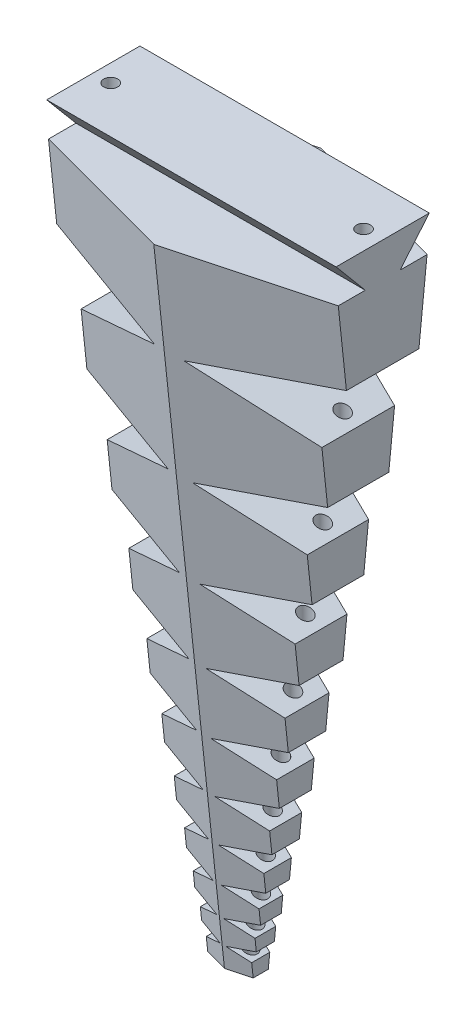
SolidWorks part; units mm, degrees
ref_plane "Front Plane" through (0, 0, 0) normal (0, 0, 1) x (1, 0, 0)
ref_plane "Top Plane" through (0, 0, 0) normal (0, 1, 0) x (1, 0, 0)
ref_plane "Right Plane" through (0, 0, 0) normal (1, 0, 0) x (0, 0, -1)
sketch "spiral_flat" plane through (0, 0, 0) normal (0, 0, 1) x (1, 0, 0)
  line L0 (3.2655, 0) -> (-3.2655, 0) construction
  line L1 (3.9293, 3.054) -> (-3.9293, 3.054) construction
  line L2 (4.728, 6.7288) -> (-4.728, 6.7288) construction
  line L3 (5.689, 11.1506) -> (-5.689, 11.1506) construction
  line L4 (6.8455, 16.4712) -> (-6.8455, 16.4712) construction
  line L5 (8.2369, 22.8733) -> (-8.2369, 22.8733) construction
  line L6 (9.9112, 30.5768) -> (-9.9112, 30.5768) construction
  line L7 (11.9259, 39.8461) -> (-11.9259, 39.8461) construction
  line L8 (14.35, 50.9996) -> (-14.35, 50.9996) construction
  line L9 (17.2669, 64.4202) -> (-17.2669, 64.4202) construction
  line L10 (20.7767, 80.5689) -> (-20.7767, 80.5689) construction
  line L11 (25, 100) -> (-25, 100) construction
  line L12 (0, -2.9617) -> (0, 103.8438) construction
  line L13 (3.2655, 0) -> (25, 100) construction
  line L14 (-3.2655, 0) -> (-25, 100) construction
  line L15 (0.3266, 0) -> (2.5, 100) construction
  line L16 (-0.3266, 0) -> (-2.5, 100) construction
  line L17 (-20.7767, 80.5689) -> (-20.7767, 100) construction
  line L18 (-17.2669, 64.4202) -> (-17.2669, 80.5689) construction
  line L19 (-14.35, 50.9996) -> (-14.35, 64.4202) construction
  line L20 (-11.9259, 39.8461) -> (-11.9259, 50.9996) construction
  line L21 (-9.9112, 30.5768) -> (-9.9112, 39.8461) construction
  line L22 (-8.2369, 22.8733) -> (-8.2369, 30.5768) construction
  line L23 (-6.8455, 16.4712) -> (-6.8455, 22.8733) construction
  line L24 (-5.689, 11.1506) -> (-5.689, 16.4712) construction
  line L25 (-4.728, 6.7288) -> (-4.728, 11.1506) construction
  line L26 (-3.9293, 3.054) -> (-3.9293, 6.7288) construction
  line L27 (-3.2655, 0) -> (-3.2655, 3.054) construction
  line L28 (20.7767, 80.5689) -> (20.7767, 100) construction
  line L29 (14.35, 50.9996) -> (14.35, 64.4202) construction
  line L30 (17.2669, 64.4202) -> (17.2669, 80.5689) construction
  line L31 (11.9259, 39.8461) -> (11.9259, 50.9996) construction
  line L32 (9.9112, 30.5768) -> (9.9112, 39.8461) construction
  line L33 (8.2369, 22.8733) -> (8.2369, 30.5768) construction
  line L34 (6.8455, 16.4712) -> (6.8455, 22.8733) construction
  line L35 (5.689, 11.1506) -> (5.689, 16.4712) construction
  line L36 (4.728, 6.7288) -> (4.728, 11.1506) construction
  line L37 (3.9293, 3.054) -> (3.9293, 6.7288) construction
  line L38 (3.2655, 0) -> (3.2655, 3.054) construction
  line L39 (-2.0777, 80.5689) -> (-17.2669, 75.0404) construction
  line L40 (-1.7267, 64.4202) -> (-17.2669, 67.1604) construction
  line L41 (-2.0777, 80.5689) -> (-20.7767, 83.866) construction
  line L42 (-1.7267, 64.4202) -> (-14.35, 59.8257) construction
  line L43 (-1.435, 50.9996) -> (-14.35, 53.2769) construction
  line L44 (-1.435, 50.9996) -> (-11.9259, 47.1812) construction
  line L45 (-1.1926, 39.8461) -> (-11.9259, 41.7387) construction
  line L46 (-1.1926, 39.8461) -> (-9.9112, 36.6728) construction
  line L47 (-0.9911, 30.5768) -> (-9.9112, 32.1496) construction
  line L48 (-0.9911, 30.5768) -> (-8.2369, 27.9395) construction
  line L49 (-0.8237, 22.8733) -> (-8.2369, 24.1805) construction
  line L50 (-0.8237, 22.8733) -> (-6.8455, 20.6816) construction
  line L51 (-0.6845, 16.4712) -> (-6.8455, 17.5576) construction
  line L52 (-0.6845, 16.4712) -> (-5.689, 14.6497) construction
  line L53 (-0.5689, 11.1506) -> (-5.689, 12.0534) construction
  line L54 (-0.5689, 11.1506) -> (-4.728, 9.6368) construction
  line L55 (-0.4728, 6.7288) -> (-4.728, 7.4791) construction
  line L56 (-0.4728, 6.7288) -> (-3.9293, 5.4708) construction
  line L57 (-0.3929, 3.054) -> (-3.9293, 3.6776) construction
  line L58 (-0.3929, 3.054) -> (-3.2655, 2.0085) construction
  line L59 (0.3929, 3.054) -> (3.2655, 2.0085) construction
  line L60 (0.3929, 3.054) -> (3.9293, 3.6776) construction
  line L61 (0.4728, 6.7288) -> (3.9293, 5.4708) construction
  line L62 (0.4728, 6.7288) -> (4.728, 7.4791) construction
  line L63 (0.5689, 11.1506) -> (4.728, 9.6368) construction
  line L64 (0.5689, 11.1506) -> (5.689, 12.0534) construction
  line L65 (0.6845, 16.4712) -> (5.689, 14.6497) construction
  line L66 (0.6845, 16.4712) -> (6.8455, 17.5576) construction
  line L67 (0.8237, 22.8733) -> (6.8455, 20.6816) construction
  line L68 (0.8237, 22.8733) -> (8.2369, 24.1805) construction
  line L69 (0.9911, 30.5768) -> (8.2369, 27.9395) construction
  line L70 (0.9911, 30.5768) -> (9.9112, 32.1496) construction
  line L71 (1.1926, 39.8461) -> (9.9112, 36.6728) construction
  line L72 (1.1926, 39.8461) -> (11.9259, 41.7387) construction
  line L73 (1.435, 50.9996) -> (11.9259, 47.1812) construction
  line L74 (1.435, 50.9996) -> (14.35, 53.2769) construction
  line L75 (1.7267, 64.4202) -> (14.35, 59.8257) construction
  line L76 (1.7267, 64.4202) -> (17.2669, 67.1604) construction
  line L77 (2.0777, 80.5689) -> (17.2669, 75.0404) construction
  line L78 (2.0777, 80.5689) -> (20.7767, 83.866) construction
  line L143 (-20.7767, 100) -> (-25, 100)
  line L144 (-25, 100) -> (-3.2655, 0)
  line L145 (-3.2655, 0) -> (-3.2655, 2.0085)
  line L146 (-0.3929, 3.054) -> (-3.9293, 3.6776)
  line L147 (-3.9293, 5.4708) -> (-0.4728, 6.7288)
  line L148 (-4.728, 7.4791) -> (-4.728, 9.6368)
  line L149 (-0.5689, 11.1506) -> (-5.689, 12.0534)
  line L150 (-5.689, 14.6497) -> (-0.6845, 16.4712)
  line L151 (-6.8455, 17.5576) -> (-6.8455, 20.6816)
  line L152 (-0.8237, 22.8733) -> (-8.2369, 24.1805)
  line L153 (-9.9112, 36.6728) -> (-1.1926, 39.8461)
  line L154 (-1.1926, 39.8461) -> (-11.9259, 41.7387)
  line L155 (-14.35, 59.8257) -> (-1.7267, 64.4202)
  line L156 (-1.7267, 64.4202) -> (-17.2669, 67.1604)
  line L157 (-17.2669, 75.0404) -> (-2.0777, 80.5689)
  line L158 (-20.7767, 83.866) -> (-20.7767, 100)
  line L159 (3.2655, 2.0085) -> (3.2655, 0)
  line L160 (0.3929, 3.054) -> (3.2655, 2.0085)
  line L161 (3.9293, 3.6776) -> (0.3929, 3.054)
  line L162 (3.9293, 5.4708) -> (3.9293, 3.6776)
  line L163 (0.4728, 6.7288) -> (3.9293, 5.4708)
  line L164 (4.728, 7.4791) -> (0.4728, 6.7288)
  line L165 (4.728, 9.6368) -> (4.728, 7.4791)
  line L166 (0.5689, 11.1506) -> (4.728, 9.6368)
  line L167 (5.689, 12.0534) -> (0.5689, 11.1506)
  line L168 (5.689, 14.6497) -> (5.689, 12.0534)
  line L169 (0.6845, 16.4712) -> (5.689, 14.6497)
  line L170 (6.8455, 17.5576) -> (0.6845, 16.4712)
  line L171 (6.8455, 20.6816) -> (6.8455, 17.5576)
  line L172 (0.8237, 22.8733) -> (6.8455, 20.6816)
  line L173 (8.2369, 24.1805) -> (0.8237, 22.8733)
  line L174 (8.2369, 27.9395) -> (8.2369, 24.1805)
  line L175 (0.9911, 30.5768) -> (8.2369, 27.9395)
  line L176 (9.9112, 32.1496) -> (0.9911, 30.5768)
  line L177 (9.9112, 36.6728) -> (9.9112, 32.1496)
  line L178 (1.1926, 39.8461) -> (9.9112, 36.6728)
  line L179 (11.9259, 41.7387) -> (1.1926, 39.8461)
  line L180 (11.9259, 47.1812) -> (11.9259, 41.7387)
  line L181 (1.435, 50.9996) -> (11.9259, 47.1812)
  line L182 (14.35, 53.2769) -> (1.435, 50.9996)
  line L183 (14.35, 59.8257) -> (14.35, 53.2769)
  line L184 (1.7267, 64.4202) -> (14.35, 59.8257)
  line L185 (17.2669, 67.1604) -> (1.7267, 64.4202)
  line L186 (17.2669, 75.0404) -> (17.2669, 67.1604)
  line L187 (2.0777, 80.5689) -> (17.2669, 75.0404)
  line L188 (20.7767, 83.866) -> (2.0777, 80.5689)
  line L189 (20.7767, 100) -> (20.7767, 83.866)
  line L190 (25, 100) -> (3.2655, 0)
  line L191 (20.7767, 100) -> (25, 100)
  line L192 (-20.7767, 83.866) -> (-2.0777, 80.5689)
  line L193 (-17.2669, 75.0404) -> (-17.2669, 67.1604)
  line L194 (-14.35, 59.8257) -> (-14.35, 53.2769)
  line L195 (-14.35, 53.2769) -> (-1.435, 50.9996)
  line L196 (-1.435, 50.9996) -> (-11.9259, 47.1812)
  line L197 (-11.9259, 47.1812) -> (-11.9259, 41.7387)
  line L198 (-9.9112, 36.6728) -> (-9.9112, 32.1496)
  line L199 (-9.9112, 32.1496) -> (-0.9911, 30.5768)
  line L200 (-0.9911, 30.5768) -> (-8.2369, 27.9395)
  line L201 (-8.2369, 27.9395) -> (-8.2369, 24.1805)
  line L202 (-6.8455, 20.6816) -> (-0.8237, 22.8733)
  line L203 (-6.8455, 17.5576) -> (-0.6845, 16.4712)
  line L204 (-5.689, 14.6497) -> (-5.689, 12.0534)
  line L205 (-0.5689, 11.1506) -> (-4.728, 9.6368)
  line L206 (-4.728, 7.4791) -> (-0.4728, 6.7288)
  line L207 (-3.9293, 5.4708) -> (-3.9293, 3.6776)
  line L208 (-0.3929, 3.054) -> (-3.2655, 2.0085)
  spline S0 degree 3 poles (0, 0) (0, 1.018) (0, 3.261) (0, 6.9778) (0, 11.4502) (0, 16.8317) (0, 23.3071) (0, 31.0987) (0, 40.4742) (0, 51.7553) (0, 65.3296) (0, 81.663) (0, 93.523) (0, 100) knots 0 0 0 0 0.03054 0.067288 0.111506 0.164712 0.228733 0.305768 0.398461 0.509996 0.644202 0.805689 1 1 1 1
  point P39 (0, 3.054)
  point P40 (0, 6.7288)
  point P41 (0, 11.1506)
  point P42 (0, 16.4712)
  point P43 (0, 22.8733)
  point P44 (0, 30.5768)
  point P45 (0, 39.8461)
  point P46 (0, 50.9996)
  point P47 (0, 64.4202)
  point P48 (0, 80.5689)
  point P49 (-0.3266, 0)
  point P50 (-0.3929, 3.054)
  point P51 (-0.4728, 6.7288)
  point P52 (-0.5689, 11.1506)
  point P53 (-0.6845, 16.4712)
  point P54 (-0.8237, 22.8733)
  point P55 (-0.9911, 30.5768)
  point P56 (-1.1926, 39.8461)
  point P57 (-1.435, 50.9996)
  point P58 (-1.7267, 64.4202)
  point P59 (-2.0777, 80.5689)
  point P60 (-2.5, 100)
  point P61 (0.3266, 0)
  point P62 (0.3929, 3.054)
  point P63 (0.4728, 6.7288)
  point P64 (0.5689, 11.1506)
  point P65 (0.6845, 16.4712)
  point P66 (0.8237, 22.8733)
  point P67 (0.9911, 30.5768)
  point P68 (1.1926, 39.8461)
  point P69 (1.435, 50.9996)
  point P70 (1.7267, 64.4202)
  point P71 (2.0777, 80.5689)
  point P72 (2.5, 100)
  dimension "D1" = 100
  dimension "D3" = 7.8586
  dimension "D2" = 6.531
  dimension "D4" = 9.456
  dimension "D5" = 11.3781
  dimension "D6" = 13.6909
  dimension "D7" = 16.4738
  dimension "D8" = 19.8224
  dimension "D9" = 23.8517
  dimension "D10" = 28.7
  dimension "D11" = 34.5338
  dimension "D12" = 41.5535
  dimension "D13" = 50
  dimension "D14" = 0.6531
  dimension "D15" = 0.7859
  dimension "D16" = 0.9456
  dimension "D17" = 1.1378
  dimension "D18" = 1.3691
  dimension "D19" = 1.6474
  dimension "D20" = 1.9822
  dimension "D21" = 2.3852
  dimension "D22" = 2.87
  dimension "D23" = 3.4534
  dimension "D24" = 4.1553
  dimension "D25" = 5
  dimension "D26" = 20
  dimension "D27" = 10
  dimension "D28" = 10
  dimension "D29" = 20
  dimension "D30" = 10
  dimension "D31" = 20
  dimension "D32" = 10
  dimension "D33" = 20
  dimension "D34" = 10
  dimension "D35" = 20
  dimension "D36" = 10
  dimension "D37" = 20
  dimension "D38" = 10
  dimension "D39" = 20
  dimension "D40" = 10
  dimension "D41" = 20
  dimension "D42" = 10
  dimension "D43" = 20
  dimension "D44" = 10
  dimension "D45" = 20
sketch "Sketch2" plane through (0, 0, 0) normal (0, 1, 0) x (1, 0, 0)
  line L0 (3.2655, 0) -> (-3.2384, 0) construction
  line L1 (0.0136, -1.9593) -> (0.0136, 1.9593) construction
  line L2 (3.2655, -1.9593) -> (3.2655, 1.9593) construction
  line L3 (-3.2384, -1.9593) -> (-3.2384, 1.9593) construction
  line L4 (3.2655, 1.9593) -> (-3.2384, 1.9593) construction
  line L5 (0.0136, 1.9593) -> (3.2655, 1.088) construction
  line L6 (3.2655, -1.9593) -> (-3.2384, -1.9593) construction
  line L7 (0.0136, -1.9593) -> (3.2655, -1.088) construction
  line L8 (0.0136, -1.9593) -> (-3.2384, -1.088) construction
  line L9 (0.0136, 1.9593) -> (-3.2384, 1.088) construction
  line L10 (0.0136, 1.9593) -> (-3.2384, 1.088)
  line L11 (-3.2384, 1.088) -> (-3.2384, -1.088)
  line L12 (-3.2384, -1.088) -> (0.0136, -1.9593)
  line L13 (0.0136, -1.9593) -> (3.2655, -1.088)
  line L14 (3.2655, -1.088) -> (3.2655, 1.088)
  line L15 (3.2655, 1.088) -> (0.0136, 1.9593)
  point P7 (0.0136, 0)
  dimension "D1" = 3.9186
  dimension "D2" = 15
ref_plane "Plane1" through (0, 100, 0) normal (0, 1, 0) x (1, 0, 0)
sketch "Sketch3" plane through (0, 100, 0) normal (0, 1, 0) x (1, 0, 0)
  line L2 (-0.1234, -12.5) -> (-0.1234, 12.5) construction
  line L5 (24.7531, 12.5) -> (-25, 12.5) construction
  line L6 (-0.1234, 12.5) -> (-25, 5.8343) construction
  line L7 (24.7531, -12.5) -> (-25, -12.5) construction
  line L8 (-0.1234, -12.5) -> (-25, -5.8343) construction
  line L9 (-0.1234, -12.5) -> (24.7531, -5.8343) construction
  line L10 (-0.1234, 12.5) -> (24.7531, 5.8343) construction
  line L12 (-25, -12.5) -> (-25, 12.5) construction
  line L15 (24.7531, -12.5) -> (24.7531, 12.5) construction
  line L16 (-0.1234, 12.5) -> (-25, 5.8343)
  line L17 (-25, 5.8343) -> (-25, -5.8343)
  line L18 (-25, -5.8343) -> (-0.1234, -12.5)
  line L19 (-0.1234, -12.5) -> (24.7531, -5.8343)
  line L20 (24.7531, -5.8343) -> (24.7531, 5.8343)
  line L21 (24.7531, 5.8343) -> (-0.1234, 12.5)
  point P8 (-0.1234, 0)
  dimension "D1" = 25
  dimension "D2" = 15
  dimension "D3" = 0.1234
  dimension "D4" = 24.8766
loft "Loft1" add profiles "Sketch2", "Sketch3" connector at (3.2655, 0, -1.0879) connector at (24.7531, 100, -5.8343)
extrude "Cut-Extrude2" cut sketch "spiral_flat" against normal through all both and the other way through all contours L192 L157 L193 L156 L155 L194 L195 L196 L197 L154 L153 L198 L199 L200 L201 L152 L202 L151 L203 L150 L204 L149 L205 L148 L206 L147 L207 L146 L208 L145 L144 L143 L158 | L188 L187 L186 L185 L184 L183 L182 L181 L180 L179 L178 L177 L176 L175 L174 L173 L172 L171 L170 L169 L168 L167 L166 L165 L164 L163 L162 L161 L160 L159 L190 L191 L189
ref_plane "Plane3" through (-20.7767, 0, 0) normal (-1, 0, 0) x (0, 0, 1)
sketch "Sketch6" plane through (-20.7767, 0, 0) normal (-1, 0, 0) x (0, 0, 1)
  line L0 (0, 100) -> (0, 83.866) construction
  line L1 (26.7585, 100) -> (-26.7585, 100) construction
  line L2 (-5.2594, 83.866) -> (5.2594, 83.866) construction
  line L3 (24.3259, 95) -> (-24.3259, 95) construction
  line L4 (2.5, 95) -> (6.6955, 100) construction
  line L5 (-2.5, 95) -> (-6.6955, 100) construction
  line L6 (2.5, 95) -> (6.6955, 100)
  line L7 (6.6955, 100) -> (6.966, 100)
  line L8 (6.966, 100) -> (5.2594, 83.866) construction
  line L9 (6.966, 100) -> (6.4371, 95)
  line L10 (6.4371, 95) -> (2.5, 95)
  line L11 (-2.5, 95) -> (-6.6955, 100)
  line L12 (-6.6955, 100) -> (-6.966, 100)
  line L13 (-6.966, 100) -> (-6.4371, 95)
  line L14 (-5.2594, 83.866) -> (-6.966, 100) construction
  line L15 (-6.4371, 95) -> (-2.5, 95)
  point P6 (0, 95)
  point P7 (-2.5, 95)
  point P10 (0, 95)
  point P11 (2.5, 95)
  dimension "D1" = 5
  dimension "D2" = 5
  dimension "D3" = 50
sketch "Sketch16" plane through (0, 0, 0) normal (0, -1, 0) x (-1, 0, 0)
  line L0 (-0.0136, -1.9593) -> (-0.0136, 1.9593) construction
  line L1 (-3.2655, 0) -> (3.2384, 0) construction
  circle A0 centre (1.7364, 0) radius 1
  circle A1 centre (-1.7636, 0) radius 1
  point P4 (-1.7636, 0)
  point P5 (1.7364, 0)
  dimension "D2" = 2
  dimension "D1" = 3.5
sketch "Sketch17" plane through (0, 100, 0) normal (0, 1, 0) x (1, 0, 0)
  line L0 (-0.1234, 12.5) -> (-0.1234, -12.5) construction
  line L1 (-20.7767, 0) -> (20.7767, 0) construction
  line L2 (-20.7767, -24.3259) -> (-20.7767, 24.3259) construction
  line L3 (20.7767, 6.8998) -> (20.7767, -6.8998) construction
  circle A1 centre (-18.2767, 0) radius 1
  circle A2 centre (18.0299, 0) radius 1
  point P10 (-18.2767, 0)
  point P17 (18.0299, 0)
  dimension "D2" = 2
  dimension "D1" = 2.5
sketch3d "3DSketch1"
  line L0 (18.0299, 100, 0) -> (1.7636, 0, 0) construction
  line L1 (-18.2767, 100, 0) -> (-1.7364, 0, 0) construction
sketch3d "3DSketch2"
  line L0 (-18.2767, 100, 0) -> (-18.2767, 79.6825, 0) construction
  line L1 (18.0299, 100, 0) -> (18.0299, 79.6788, 0) construction
extrude "Cut-Extrude3" cut sketch "Sketch17" against normal blind 20 contours A1 | A2
ref_plane "Plane5" through (0, 80.5689, 0) normal (0, -1, 0) x (-1, 0, 0)
sketch "Sketch22" plane through (0, 80.5689, 0) normal (0, -1, 0) x (-1, 0, 0)
  line L0 (18.2767, 0) -> (-18.0299, 0) construction
  line L2 (0.1234, -12.5) -> (0.1234, 12.5) construction
  circle A0 centre (15.2767, 0) radius 1
  circle A1 centre (-15.0299, 0) radius 1
  point P4 (15.2767, 0)
  point P11 (-15.0299, 0)
  dimension "D2" = 2
  dimension "D1" = 3
extrude "Cut-Extrude4" cut sketch "Sketch22" along normal blind 20
ref_plane "Plane6" through (0, 64.4202, 0) normal (0, -1, 0) x (-1, 0, 0)
sketch "Sketch23" plane through (0, 64.4202, 0) normal (0, -1, 0) x (-1, 0, 0)
  line L0 (15.2767, 0) -> (-15.0299, 0) construction
  line L1 (0.0549, 7.2297) -> (0.0549, -7.2297) construction
  line L2 (-0.0136, 1.9593) -> (0.1234, 12.5) construction
  line L3 (-0.0136, -1.9593) -> (0.1234, -12.5) construction
  circle A0 centre (12.2767, 0) radius 1
  circle A1 centre (-12.1669, 0) radius 1
  point P10 (12.2767, 0)
  point P13 (-12.1669, 0)
  dimension "D2" = 2
  dimension "D1" = 3
extrude "Cut-Extrude5" cut sketch "Sketch23" along normal blind 15
ref_plane "Plane7" through (0, 50.9996, 0) normal (0, -1, 0) x (-1, 0, 0)
sketch "Sketch24" plane through (0, 50.9996, 0) normal (0, -1, 0) x (-1, 0, 0)
  line L0 (-12.1669, 0) -> (12.2767, 0) construction
  line L1 (0.0549, -7.7763) -> (0.0549, 7.7763) construction
  circle A0 centre (9.7767, 0) radius 1
  circle A1 centre (-9.6669, 0) radius 1
  point P4 (9.7767, 0)
  point P7 (0.0549, 0)
  point P10 (-9.6669, 0)
  dimension "D2" = 2
  dimension "D1" = 2.5
extrude "Cut-Extrude6" cut sketch "Sketch24" along normal blind 12
ref_plane "Plane8" through (0, 39.8461, 0) normal (0, -1, 0) x (-1, 0, 0)
sketch "Sketch25" plane through (0, 39.8461, 0) normal (0, -1, 0) x (-1, 0, 0)
  line L0 (9.7767, 0) -> (-9.6669, 0) construction
  line L1 (0, 0) -> (0.0549, 7.2297) construction
  line L2 (-0.0136, 1.9593) -> (0.1234, 12.5) construction
  line L3 (0, 0) -> (0.0549, -7.2297) construction
  circle A0 centre (7.7767, 0) radius 1
  circle A1 centre (-7.7758, 0.1182) radius 1
  point P10 (7.7767, 0)
  point P13 (-7.7758, 0.1182)
  dimension "D2" = 2
  dimension "D1" = 2
extrude "Cut-Extrude7" cut sketch "Sketch25" along normal blind 10
ref_plane "Plane9" through (0, 30.5768, 0) normal (0, -1, 0) x (-1, 0, 0)
sketch "Sketch26" plane through (0, 30.5768, 0) normal (0, -1, 0) x (-1, 0, 0)
  line L0 (-9.6669, 0) -> (9.7767, 0) construction
  line L1 (0.0549, 6.0441) -> (0.0549, -6.0441) construction
  circle A0 centre (-6.1669, 0) radius 1
  circle A1 centre (6.2767, 0) radius 1
  point P4 (-6.1669, 0)
  point P7 (6.2767, 0)
  point P10 (0.0549, 0)
  dimension "D2" = 2
  dimension "D1" = 3.5
extrude "Cut-Extrude8" cut sketch "Sketch26" along normal blind 8
ref_plane "Plane10" through (0, 22.8733, 0) normal (0, -1, 0) x (-1, 0, 0)
sketch "Sketch27" plane through (0, 22.8733, 0) normal (0, -1, 0) x (-1, 0, 0)
  line L0 (6.2767, 0) -> (-6.1669, 0) construction
  line L1 (0.0549, -5.3055) -> (0.0549, 5.3055) construction
  circle A0 centre (5.0767, 0) radius 1
  circle A1 centre (-4.9669, 0) radius 1
  point P4 (5.0767, 0)
  point P7 (0.0549, 0)
  point P10 (-4.9669, 0)
  dimension "D2" = 2
  dimension "D1" = 1.2
extrude "Cut-Extrude9" cut sketch "Sketch27" along normal blind 6 contours A1 | A0
ref_plane "Plane11" through (0, 16.4712, 0) normal (0, -1, 0) x (-1, 0, 0)
sketch "Sketch28" plane through (0, 16.4712, 0) normal (0, -1, 0) x (-1, 0, 0)
  line L0 (5.0767, 0) -> (-4.9669, 0) construction
  line L1 (0.0549, -4.5751) -> (0.0549, 4.5751) construction
  circle A0 centre (4.0767, 0) radius 1
  circle A1 centre (-3.9669, 0) radius 1
  point P4 (4.0767, 0)
  point P7 (0.0549, 0)
  point P10 (-3.9669, 0)
  dimension "D2" = 2
  dimension "D1" = 1
extrude "Cut-Extrude10" cut sketch "Sketch28" along normal blind 6
ref_plane "Plane12" through (0, 11.1506, 0) normal (0, -1, 0) x (-1, 0, 0)
sketch "Sketch29" plane through (0, 11.1506, 0) normal (0, -1, 0) x (-1, 0, 0)
  line L0 (4.0767, 0) -> (-3.9669, 0) construction
  line L1 (0, -3.6608) -> (0, 3.6608) construction
  circle A0 centre (3.2767, 0) radius 1
  circle A1 centre (-3.2767, 0) radius 1
  point P4 (3.2767, 0)
  point P8 (0, 0)
  point P11 (-3.2767, 0)
  dimension "D2" = 2
  dimension "D1" = 0.8
extrude "Cut-Extrude11" cut sketch "Sketch29" along normal blind 5
ref_plane "Plane13" through (0, 6.7288, 0) normal (0, -1, 0) x (-1, 0, 0)
sketch "Sketch30" plane through (0, 6.7288, 0) normal (0, -1, 0) x (-1, 0, 0)
  line L0 (3.2767, 0) -> (-3.2767, 0) construction
  line L1 (0, -4.9829) -> (0, 4.9829) construction
  circle A0 centre (2.4767, 0) radius 1
  circle A1 centre (-2.4767, 0) radius 1
  point P4 (2.4767, 0)
  point P8 (0, 0)
  point P11 (-2.4767, 0)
  dimension "D2" = 2
  dimension "D1" = 0.8
extrude "Cut-Extrude12" cut sketch "Sketch30" along normal blind 4
extrude "Cut-Extrude13" cut sketch "Sketch16" against normal blind 3 contours A0 | A1
ref_plane "Plane14" through (20.8299, 0, 0) normal (1, 0, 0) x (0, 0, -1)
sketch "Sketch31" plane through (20.8299, 0, 0) normal (1, 0, 0) x (0, 0, -1)
  line L0 (0, 100) -> (0, 83.866) construction
  line L1 (26.7527, 95) -> (2.5, 95)
  line L2 (2.5, 95) -> (6.6955, 100)
  line L3 (6.6955, 100) -> (26.7527, 100)
  line L4 (22.8545, 100) -> (-22.8545, 100) construction
  line L5 (26.7527, 100) -> (26.7527, 95)
  line L6 (-6.6955, 100) -> (-26.7527, 100)
  line L7 (-2.5, 95) -> (-6.6955, 100)
  line L8 (-26.7527, 95) -> (-2.5, 95)
  line L9 (-26.7527, 100) -> (-26.7527, 95)
  dimension "D1" = 50
extrude "Cut-Extrude14" cut sketch "Sketch31" against normal blind 50
